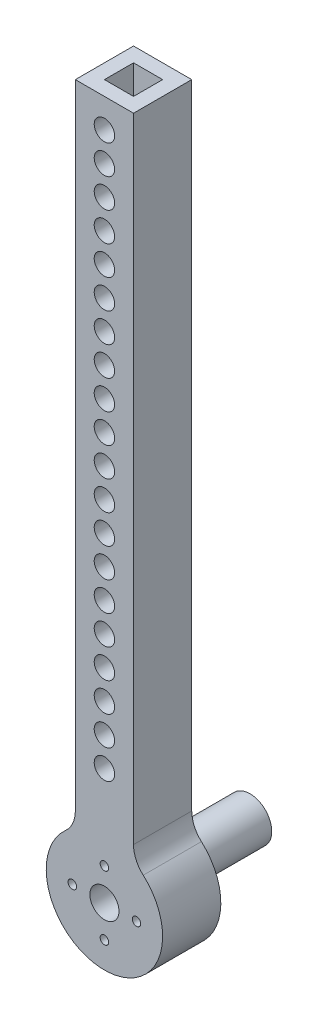
SolidWorks part; units mm, degrees
ref_plane "Front Plane" through (0, 0, 0) normal (0, 0, 1) x (1, 0, 0)
ref_plane "Top Plane" through (0, 0, 0) normal (0, 1, 0) x (1, 0, 0)
ref_plane "Right Plane" through (0, 0, 0) normal (1, 0, 0) x (0, 0, -1)
sketch "Sketch1" plane through (0, 0, 0) normal (0, 1, 0) x (1, 0, 0)
  line L0 (-3.175, -3.175) -> (-3.175, 3.175)
  line L1 (-6.35, -6.35) -> (6.35, -6.35)
  line L2 (-6.35, -6.35) -> (-6.35, 6.35)
  line L3 (-6.35, 6.35) -> (6.35, 6.35)
  line L4 (6.35, -6.35) -> (6.35, 6.35)
  line L5 (-6.35, -6.35) -> (6.35, 6.35) construction
  line L6 (-6.35, 6.35) -> (6.35, -6.35) construction
  line L7 (-3.175, 3.175) -> (3.175, 3.175)
  line L8 (3.175, -3.175) -> (3.175, 3.175)
  line L9 (-3.175, -3.175) -> (3.175, -3.175)
  point P0 (0, 0)
  dimension "D1" = 12.7
  dimension "D2" = 3.175
extrude "Boss-Extrude1" add sketch "Sketch1" along normal blind 152.4
sketch "Sketch2" plane through (0, 0, 6.35) normal (0, 0, 1) x (1, 0, 0)
  line L0 (-6.35, 0) -> (6.35, 0) construction
  circle A0 centre (0, 25.4) radius 2.227
  circle A10 centre (0, 31.75) radius 2.227
  circle A11 centre (0, 38.1) radius 2.227
  circle A12 centre (0, 44.45) radius 2.227
  circle A13 centre (0, 50.8) radius 2.227
  circle A14 centre (0, 57.15) radius 2.227
  circle A15 centre (0, 63.5) radius 2.227
  circle A16 centre (0, 69.85) radius 2.227
  circle A17 centre (0, 76.2) radius 2.227
  circle A18 centre (0, 82.55) radius 2.227
  circle A19 centre (0, 88.9) radius 2.227
  circle A20 centre (0, 95.25) radius 2.227
  circle A21 centre (0, 101.6) radius 2.227
  circle A22 centre (0, 107.95) radius 2.227
  circle A23 centre (0, 114.3) radius 2.227
  circle A24 centre (0, 120.65) radius 2.227
  circle A25 centre (0, 127) radius 2.227
  circle A26 centre (0, 133.35) radius 2.227
  circle A27 centre (0, 139.7) radius 2.227
  circle A28 centre (0, 146.05) radius 2.227
  dimension "D2" = 4.454
  dimension "D1" = 25.4
  dimension "D3" = 20
extrude "Cut-Extrude1" cut sketch "Sketch2" against normal through all
sketch "Sketch3" plane through (0, 0, 6.35) normal (0, 0, 1) x (1, 0, 0)
  circle A0 centre (0, 0) radius 12.7
  dimension "D1" = 25.4
extrude "Boss-Extrude2" add sketch "Sketch3" against normal blind 12.7
sketch "Sketch4" plane through (0, 0, 6.35) normal (0, 0, 1) x (1, 0, 0)
  circle A0 centre (0, 0) radius 4.7625
  dimension "D1" = 9.525
extrude "Boss-Extrude3" add sketch "Sketch4" against normal blind 31.75
sketch "Sketch6" plane through (0, 0, 6.35) normal (0, 0, 1) x (1, 0, 0)
  circle A0 centre (0, 0) radius 3.175
  circle A1 centre (7, 0) radius 0.927
  circle A2 centre (0, -7) radius 0.927
  circle A3 centre (-7, 0) radius 0.927
  circle A4 centre (0, 7) radius 0.927
  point P14 (0, 0)
  dimension "D1" = 6.35
  dimension "D2" = 1.854
  dimension "D3" = 7
  dimension "D4" = 4
extrude "Cut-Extrude3" cut sketch "Sketch6" against normal through all
fillet "Fillet2" radius 6.35 2 edges at (-6.35, 10.9985, 0) (6.35, 10.9985, 0)
equation "\"tightTol\"= 0.005in"
equation "\"normTol\"= 0.01in"
equation "\"looseTol\"= 0.02in"
equation "\"Fry height\"= 0.5in"
equation "\"Fry spacing\"= 0.5625in"
equation "\"Potato width\"= \"Fry spacing\" * 4"
equation "\"Potato length\"= 80mm"
equation "\"D2@Sketch6\"=1.6mm+\"normTol\""
equation "\"D3@Sketch6\"=7mm"
